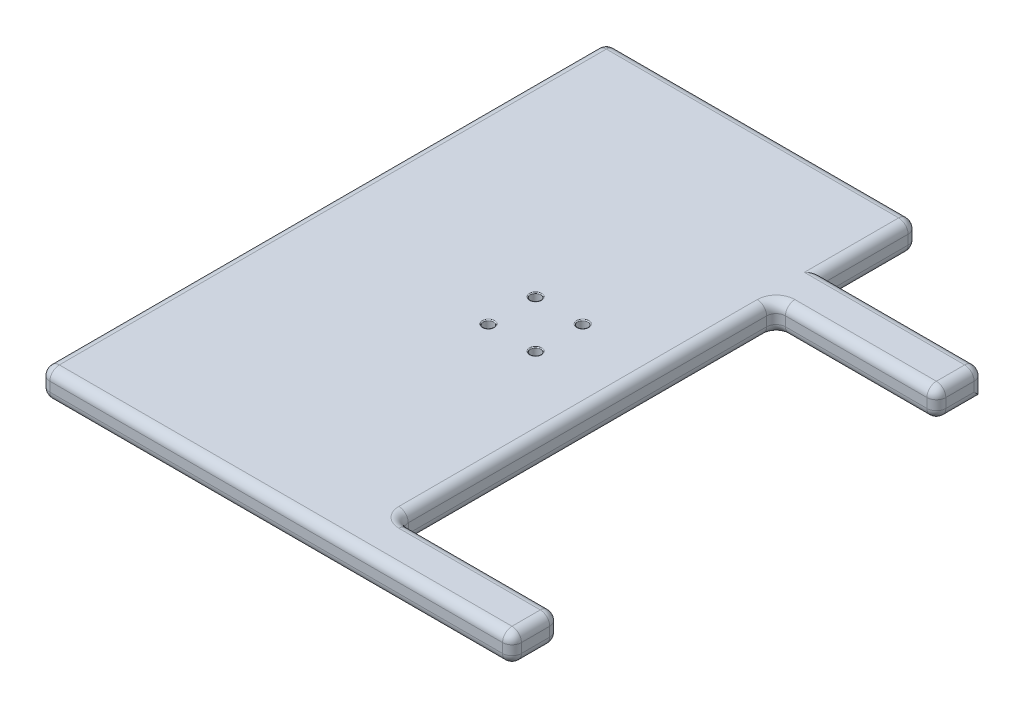
SolidWorks part; units mm, degrees
ref_plane "前视基准面" through (0, 0, 0) normal (0, 0, 1) x (1, 0, 0)
ref_plane "上视基准面" through (0, 0, 0) normal (0, 1, 0) x (1, 0, 0)
ref_plane "右视基准面" through (0, 0, 0) normal (1, 0, 0) x (0, 0, -1)
other "Configuration Table"
sketch "草图1" plane through (0, 0, 0) normal (0, 1, 0) x (1, 0, 0)
  line L1 (-60, 60) -> (6, 60)
  line L2 (-60, 60) -> (-60, -60)
  line L3 (-60, -60) -> (40, -60)
  line L4 (40, 40) -> (40, 30)
  line L5 (-55, 0) -> (55, 0) construction
  line L6 (0, -55) -> (0, 55) construction
  line L7 (6, 60) -> (6, 40)
  line L8 (6, 40) -> (40, 40)
  line L10 (40, 30) -> (6, 30)
  line L11 (6, 30) -> (6, -50)
  line L12 (6, -50) -> (40, -50)
  line L13 (40, -50) -> (40, -60)
  dimension "D1" = 6
  dimension "D2" = 6
  dimension "D3" = 60
  dimension "D4" = 120
  dimension "D5" = 40
  dimension "D6" = 20
  dimension "D7" = 10
  dimension "D8" = 60
  dimension "D9" = 10
extrude "凸台-拉伸1" add sketch "草图1" along normal blind 6
sketch "草图6" plane through (0, 0, 0) normal (0, -1, 0) x (-1, 0, 0)
  line L0 (-55, 0) -> (55, 0) construction
  line L1 (60, 60) -> (60, -60) construction
  point P0 (15, 0)
  dimension "D1" = 45
ref_axis "基准轴1" through (-15, 0, 0) along (0, -1, 0)
sketch "草图7" plane through (0, 0, 0) normal (0, -1, 0) x (1, 0, 0)
  point P0 (-20, 5)
  point P1 (-20, -5)
  point P3 (-10, 5)
  point P4 (-10, -5)
  dimension "D1" = 5
  dimension "D2" = 5
  dimension "D3" = 10
  dimension "D4" = 5
  dimension "D5" = 5
  dimension "D6" = 5
  dimension "D7" = 5
  dimension "D8" = 5
hole_wizard "M2 六角头机械螺钉的柱形沉头孔1" positions "草图8" profile "草图9" counterbore size "M2" standard "ANSI Metric" end condition up to next
sketch "草图8" plane through (0, 0, 0) normal (0, -1, 0) x (-1, 0, 0)
  point P0 (10, 5)
  point P3 (20, 5)
  point P6 (20, -5)
  point P9 (10, -5)
sketch "草图9" plane through (-10, 0, -5) normal (1, 0, 0) x (0, 0, -1)
  line L0 (0, 0) -> (0, 6)
  line L1 (0, 6) -> (1.1, 6)
  line L3 (1.1, 6) -> (1.1, 3)
  line L4 (1.1, 3) -> (2.3, 3)
  line L5 (2.3, 3) -> (2.3, 0)
  line L7 (2.3, 0) -> (0, 0)
  line L11 (0, -6.35) -> (0, 107.95) construction
  dimension "通孔孔直径" = 2.2
  dimension "通孔孔深度" = 6
  dimension "柱形沉头孔直径" = 4.6
  dimension "柱形沉头孔深度" = 3
fillet "Fillet1" radius 2 28 edges at (-10, 6, 60) (-10, 0, 60) (-60, 6, 0) (-60, 0, 0) (-60, 3, 60) (40, 3, 50) (40, 3, 60) (40, 0, 55) (40, 6, 55) (23, 0, -30) (23, 6, -30) (40, 3, -40) (40, 6, -35) (40, 0, -35) (40, 3, -30) (6, 3, -60) (6, 0, -50) (6, 6, -50) (23, 6, -40) (23, 0, 50) (23, 6, 50) (6, 3, 50) (6, 6, 10) (-27, 0, -60) (6, 0, 10) (6, 3, -30) (-27, 6, -60) (-60, 3, -60)
fillet "Fillet2" radius 0.3 4 edges at (-20, 0, -7.3) (-10, 0, -7.3) (-10, 0, 2.7) (-20, 0, 2.7)
fillet "Fillet3" radius 0.2 4 edges at (-20, 6, 6.1) (-10, 6, 6.1) (-10, 6, -3.9) (-20, 6, -3.9)
